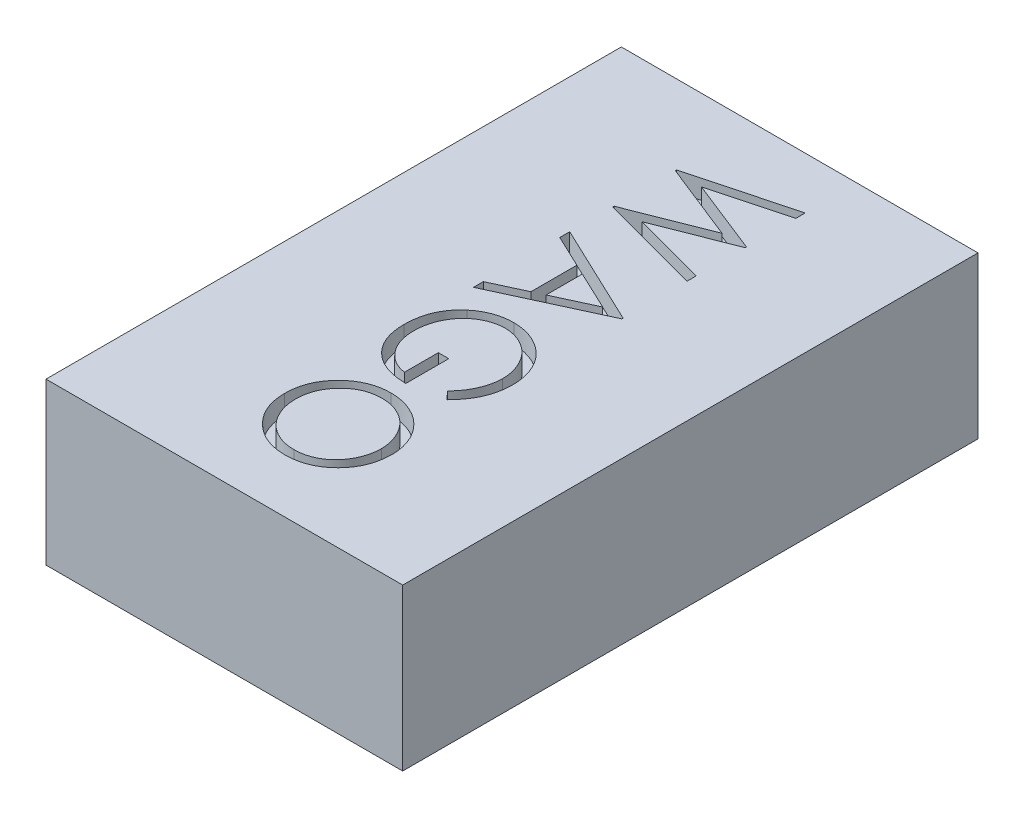
SolidWorks part; units mm, degrees
ref_plane "Front Plane" through (0, 0, 0) normal (0, 0, 1) x (1, 0, 0)
ref_plane "Top Plane" through (0, 0, 0) normal (0, 1, 0) x (1, 0, 0)
ref_plane "Right Plane" through (0, 0, 0) normal (1, 0, 0) x (0, 0, -1)
sketch "Sketch1" plane through (0, 0, 0) normal (0, 1, 0) x (1, 0, 0)
  line L1 (-9.3, 15) -> (9.3, 15)
  line L2 (-9.3, 15) -> (-9.3, -15)
  line L3 (-9.3, -15) -> (9.3, -15)
  line L4 (9.3, 15) -> (9.3, -15)
  line L5 (-9.3, 15) -> (9.3, -15) construction
  line L6 (-9.3, -15) -> (9.3, 15) construction
  point P0 (0, 0)
  dimension "D1" = 30
  dimension "D2" = 18.6
extrude "Boss-Extrude1" add sketch "Sketch1" along normal blind 8.4
sketch "Sketch2" plane through (0, 8.4, 0) normal (0, 1, 0) x (1, 0, 0)
  line L0 (-2.3, 12.6371) -> (-2.3, -10.6165) construction
  line L1 (-9.3, 15) -> (-9.3, -15) construction
  text T0 "WAGO" font "Century Gothic" height in points 20
  point P5 (-2.3, 12.6371)
  dimension "D1" = 7
extrude "Cut-Extrude1" cut sketch "Sketch2" against normal blind 1
